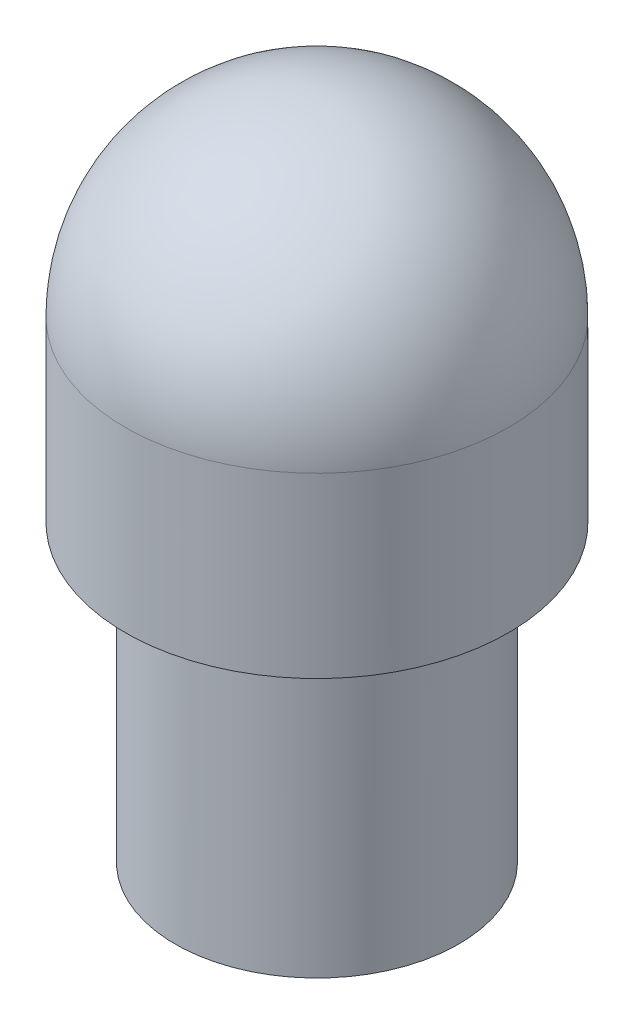
SolidWorks part; units mm, degrees
material "6061-T6 (SS)"
ref_plane "Front Plane" through (0, 0, 0) normal (0, 0, 1) x (1, 0, 0)
ref_plane "Top Plane" through (0, 0, 0) normal (0, 1, 0) x (1, 0, 0)
ref_plane "Right Plane" through (0, 0, 0) normal (1, 0, 0) x (0, 0, -1)
sketch "Sketch1" plane through (0, 0, 0) normal (0, 0, 1) x (1, 0, 0)
  line L0 (0, 25.4) -> (0, 43.6626) construction
  line L2 (4.8966, 14.7066) -> (-5.3865, 14.7066) construction
  line L3 (-5.2705, 38.3921) -> (-5.2705, 33.5026)
  line L4 (-5.2705, 33.5026) -> (-3.899, 33.5026)
  line L5 (-3.899, 33.5026) -> (-3.899, 25.4)
  line L6 (-3.899, 25.4) -> (0, 25.4)
  line L7 (0, 25.4) -> (0, 43.6626)
  arc A0 (0, 43.6626) -> (-5.2705, 38.3921) centre (0, 38.3921) ccw
  dimension "D2" = 10.541
  dimension "D1" = 28.956
  dimension "D3" = 7.798
  dimension "D4" = 18.2626
  dimension "D5" = 10.16
revolve "Revolve1" add sketch "Sketch1" angle 360 about L0
hole_wizard "M7X0.75 Tapped Hole1" positions "Sketch2" profile "Sketch3" tap size "M7X0.75" standard "ANSI Metric"
sketch "Sketch2" plane through (0, 25.4, 0) normal (0, -1, 0) x (-1, 0, 0)
  point P0 (0, 0)
cosmetic thread "Hole Thread1"
sketch "Sketch3" plane through (0, 25.4, 0) normal (1, 0, 0) x (0, 0, -1)
  line L0 (0, 0) -> (0, 17.8046)
  line L1 (0, 17.8046) -> (3, 16.002)
  line L2 (3, 16.002) -> (3, 0)
  line L5 (3, 0) -> (0, 0)
  line L10 (0, 17.8046) -> (-3, 16.002) construction
  line L11 (0, -6.35) -> (0, 107.95) construction
  dimension "Tap Drill Dia." = 6
  dimension "Tap Drill Depth" = 16.002
  dimension "Drill Angle" = 118
sketch "Sketch4" plane through (0, 25.4, 0) normal (0, -1, 0) x (1, 0, 0)
  circle A0 centre (0, 0) radius 3.5
  dimension "D1" = 7
extrude "Cut-Extrude1" cut sketch "Sketch4" against normal blind 2.5
fillet "Fillet1" radius 0.762 1 edges at (0, 33.5026, -3.899)
